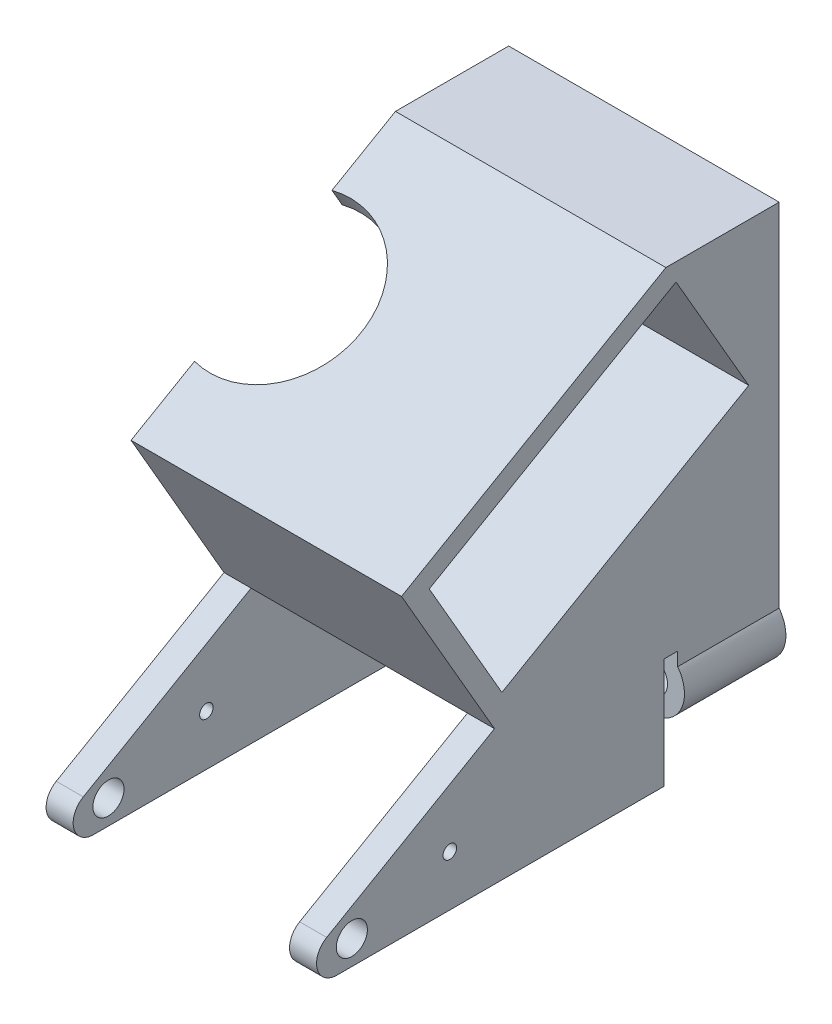
SolidWorks part; units mm, degrees
ref_plane "Alzado" through (0, 0, 0) normal (0, 0, 1) x (1, 0, 0)
ref_plane "Planta" through (0, 0, 0) normal (0, 1, 0) x (1, 0, 0)
ref_plane "Vista lateral" through (0, 0, 0) normal (1, 0, 0) x (0, 0, -1)
sketch "Croquis1" plane through (0, 0, 0) normal (0, 0, 1) x (1, 0, 0)
  line L0 (-152.0308, 99.9536) -> (-112.0308, 99.9536)
  line L1 (-152.0308, 99.9536) -> (-152.0308, 39.9536)
  line L2 (-152.0308, 39.9536) -> (-112.0308, 39.9536)
  line L3 (-112.0308, 99.9536) -> (-112.0308, 39.9536)
  circle A2 centre (-148.0308, 44.9536) radius 2.5
  circle A3 centre (-116.0308, 44.9536) radius 2.5
  dimension "D1" = 60
  dimension "D3" = 5
  dimension "D4" = 5
  dimension "D2" = 40
  dimension "D5" = 32
  dimension "D6" = 4
  dimension "D7" = 5
ref_plane "Plano1" through (0, 0, 0) normal (0, 0, 1) x (1, 0, 0)
sketch "Croquis2" plane through (0, 0, 0) normal (0, 0, 1) x (1, 0, 0)
  line L0 (-152.0308, 47.9536) -> (-152.0308, 99.9536)
  line L1 (-152.0308, 99.9536) -> (-152.0308, 39.9536) construction
  line L2 (-152.0308, 99.9536) -> (-112.0308, 99.9536)
  line L3 (-112.0308, 99.9536) -> (-112.0308, 47.9536)
  line L4 (-112.0308, 99.9536) -> (-112.0308, 39.9536) construction
  line L5 (-143.0308, 44.9536) -> (-121.0308, 44.9536)
  circle A0 centre (-148.0308, 44.9536) radius 2.5
  circle A1 centre (-116.0308, 44.9536) radius 2.5
  arc A2 (-121.0308, 44.9536) -> (-112.0308, 47.9536) centre (-116.0308, 44.9536) ccw
  arc A3 (-152.0308, 47.9536) -> (-143.0308, 44.9536) centre (-148.0308, 44.9536) ccw
extrude "Saliente-Extruir1" add sketch "Croquis2" along normal blind 3
sketch "Croquis3" plane through (-152.0308, 0, 0) normal (-1, 0, 0) x (0, 0, 1)
  line L0 (3, 99.9536) -> (16.75, 99.9536)
  line L1 (15.25, 97.3555) -> (4.5, 78.736)
  line L2 (3, 99.9536) -> (3, 47.9536) construction
  line L3 (3, 99.9536) -> (3, 76.1379)
  line L4 (3, 76.1379) -> (42.101, 53.5629)
  line L5 (4.5, 78.736) -> (41.003, 57.661)
  line L6 (41.003, 57.661) -> (51.753, 76.2805)
  line L7 (51.753, 76.2805) -> (15.25, 97.3555)
  line L8 (16.75, 99.9536) -> (55.851, 77.3786)
  line L9 (55.851, 77.3786) -> (42.101, 53.5629)
  dimension "D1" = 27.5
  dimension "D2" = 30
  dimension "D3" = 3
  dimension "D4" = 42.15
  dimension "D5" = 45.15
extrude "Saliente-Extruir2" add sketch "Croquis3" against normal up to vertex (40 mm away) up to point (-112.0308, 47.9536, 3)
sketch "Croquis4" plane through (0, 0, 3) normal (0, 0, 1) x (1, 0, 0)
  line L0 (-152.0308, 47.9536) -> (-152.0308, 49.9536)
  line L1 (-152.0308, 76.1379) -> (-152.0308, 47.9536) construction
  line L6 (-112.0308, 47.9536) -> (-112.0308, 76.1379) construction
  line L7 (-112.0308, 49.9536) -> (-112.0308, 47.9536)
  line L8 (-152.0308, 49.9536) -> (-148.0308, 49.9536)
  line L9 (-112.0308, 49.9536) -> (-116.0308, 49.9536)
  circle A0 centre (-148.0308, 44.9536) radius 2.5
  circle A2 centre (-116.0308, 44.9536) radius 2.5
  arc A4 (-152.0308, 47.9536) -> (-148.0308, 49.9536) centre (-148.0308, 44.9536) ccw
  arc A6 (-116.0308, 49.9536) -> (-112.0308, 47.9536) centre (-116.0308, 44.9536) ccw
extrude "Saliente-Extruir3" add sketch "Croquis4" along normal blind 12
sketch "Croquis6" plane through (-152.0308, 0, 0) normal (-1, 0, 0) x (0, 0, 1)
  line L0 (3, 49.9536) -> (3, 76.1379)
  line L1 (3, 76.1379) -> (66.916, 39.236)
  line L2 (65.416, 33.6379) -> (17, 33.6379)
  line L3 (17, 33.6379) -> (17, 49.9536)
  line L4 (17, 49.9536) -> (3, 49.9536)
  line L5 (15, 49.9536) -> (15, 47.9536) construction
  line L6 (68.3138, 35.8615) -> (63.1944, 37.2332) construction
  line L7 (63.1944, 37.2332) -> (48.7055, 41.1155) construction
  arc A0 (66.916, 39.236) -> (65.416, 33.6379) centre (65.416, 36.6379) cw
  circle A1 centre (63.1944, 37.2332) radius 2.3
  circle A2 centre (48.7055, 41.1155) radius 1
  point P11 (76.6122, 33.6379)
  dimension "D3" = 3
  dimension "D4" = 2
  dimension "D1" = 2
  dimension "D2" = 85
extrude "Saliente-Extruir5" add sketch "Croquis6" against normal up to vertex (4 mm away) up to point (-148.0308, 49.9536, 15)
extrude "Saliente-Extruir6" add sketch "Croquis6<2>" along normal up to vertex (-36 mm away) from surface up to point (-116.0308, 49.9536, 15) starting at face at (-112.0308, 66.9779, 16.7447)
sketch "Croquis6<2>" plane through (-152.0308, 0, 0) normal (-1, 0, 0) x (0, 0, 1) same geometry as "Croquis6"
sketch "Croquis7" plane through (0, 82.2182, 47.4687) normal (0, 0.866, 0.5) x (1, 0, 0)
  line L1 (-152.0308, 12.8959) -> (-164.5308, 12.8959) construction
  line L2 (-152.0308, -9.6791) -> (-152.0308, 35.4709) construction
  circle A0 centre (-149.5308, 12.8959) radius 12
  dimension "D2" = 15
  dimension "D1" = 12.5
extrude "Cortar-Extruir1" cut sketch "Croquis7" against normal up to vertex (3 mm away) up to point (-152.0308, 76.2805, 51.753)
